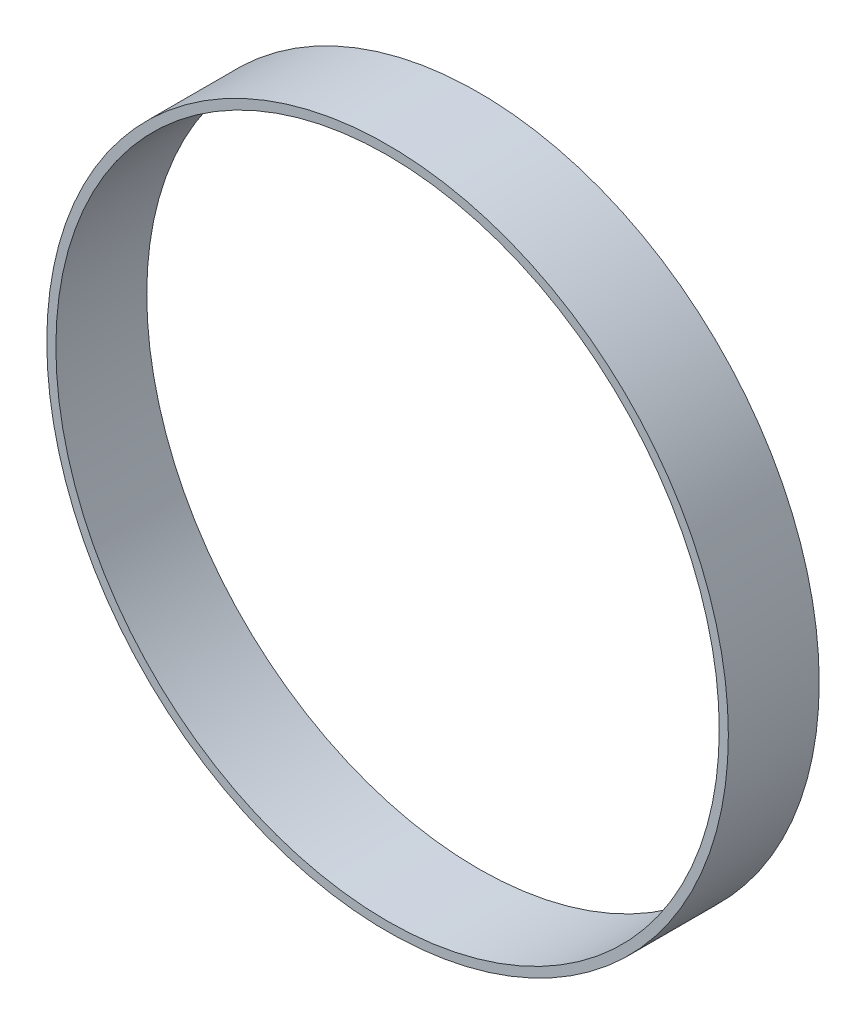
SolidWorks part; units mm, degrees
material "6061-T6 (SS)"
ref_plane "Front Plane" through (0, 0, 0) normal (0, 0, 1) x (1, 0, 0)
ref_plane "Top Plane" through (0, 0, 0) normal (0, 1, 0) x (1, 0, 0)
ref_plane "Right Plane" through (0, 0, 0) normal (1, 0, 0) x (0, 0, -1)
sketch "Sketch1" plane through (0, 0, 0) normal (0, 0, 1) x (1, 0, 0)
  circle A0 centre (0, 0) radius 73
  circle A1 centre (0, 0) radius 75
  dimension "D1" = 2
  dimension "D2" = 150
extrude "Boss-Extrude1" add sketch "Sketch1" along normal blind 10 and the other way blind 10
